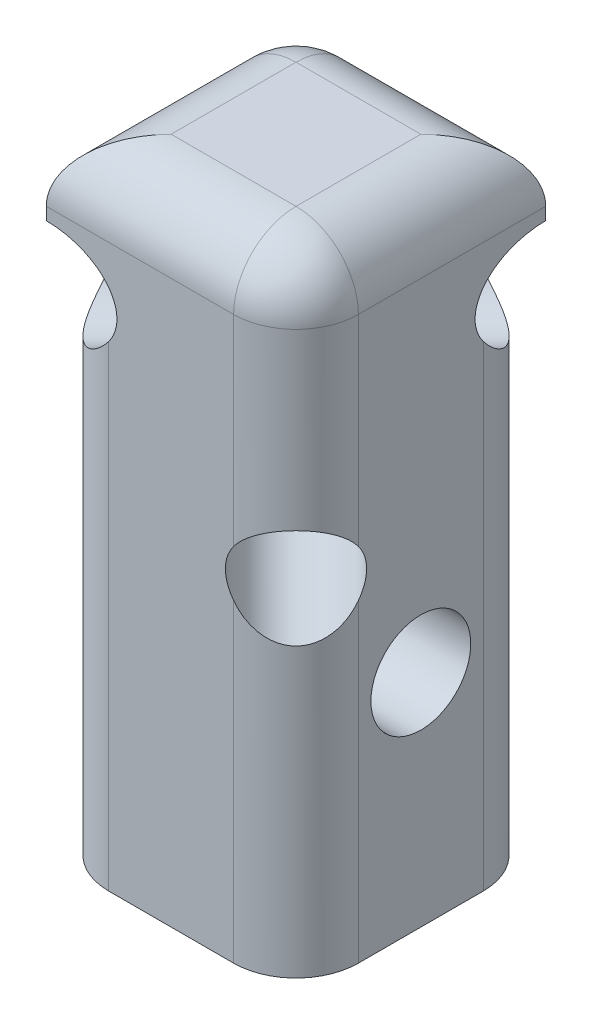
SolidWorks part; units mm, degrees
ref_plane "Front Plane" through (0, 0, 0) normal (0, 0, 1) x (1, 0, 0)
ref_plane "Top Plane" through (0, 0, 0) normal (0, 1, 0) x (1, 0, 0)
ref_plane "Right Plane" through (0, 0, 0) normal (1, 0, 0) x (0, 0, -1)
sketch "Sketch1" plane through (0, 0, 0) normal (0, 1, 0) x (1, 0, 0)
  line L1 (-3, -3) -> (3, -3)
  line L2 (-3, -3) -> (-3, 3)
  line L3 (-3, 3) -> (3, 3)
  line L4 (3, -3) -> (3, 3)
  line L5 (-3, -3) -> (3, 3) construction
  line L6 (-3, 3) -> (3, -3) construction
  point P0 (0, 0)
  dimension "D1" = 6
  dimension "D2" = 6
extrude "Boss-Extrude1" add sketch "Sketch1" along normal blind 15
sketch "Sketch2" plane through (-3, 0, 0) normal (-1, 0, 0) x (0, 0, 1)
  line L0 (-3, 0) -> (3, 0) construction
  line L2 (-3, 15) -> (3, 15) construction
  circle A0 centre (0, 5.3) radius 1.2
  point P7 (0, 15)
  point P8 (0, 0)
  dimension "D1" = 2.4
  dimension "D2" = 5.3
extrude "Cut-Extrude1" cut sketch "Sketch2" against normal blind 15
ref_axis "Axis1" through (3, 15, -3) along (-0.7071, 0, 0.7071)
ref_axis "Axis2" through (-3, 15, -3) along (0.7071, 0, 0.7071)
ref_plane "Plane1" through (3, 0, 3) normal (0.7071, 0, 0.7071) x (0.7071, 0, -0.7071)
sketch "Sketch3" plane through (3, 0, 3) normal (0.7071, 0, 0.7071) x (0.7071, 0, -0.7071)
  line L0 (0, 15) -> (0, 0) construction
  line L1 (0, 15) -> (4.2426, 15) construction
  circle A0 centre (0, 8.11) radius 1.2
  dimension "D1" = 2.4
  dimension "D2" = 6.89
extrude "Cut-Extrude3" cut sketch "Sketch3" against normal blind 15
ref_plane "Plane2" through (-3, 0, 3) normal (-0.7071, 0, 0.7071) x (0.7071, 0, 0.7071)
sketch "Sketch4" plane through (-3, 0, 3) normal (-0.7071, 0, 0.7071) x (0.7071, 0, 0.7071)
  line L0 (0, 15) -> (0, 0) construction
  line L1 (0, 15) -> (4.2426, 15) construction
  circle A0 centre (0, 12) radius 1.2
  dimension "D1" = 2.4
  dimension "D2" = 3
extrude "Cut-Extrude5" cut sketch "Sketch4" against normal blind 15
fillet "Fillet1" radius 1.5 10 edges at (0, 15, 3) (-3, 15, 0) (0, 15, -3) (3, 15, 0) (3, 12.155, 3) (-3, 5.4, 3) (3, 3.455, 3) (3, 5.4, -3) (-3, 12.155, -3) (-3, 3.455, -3)
